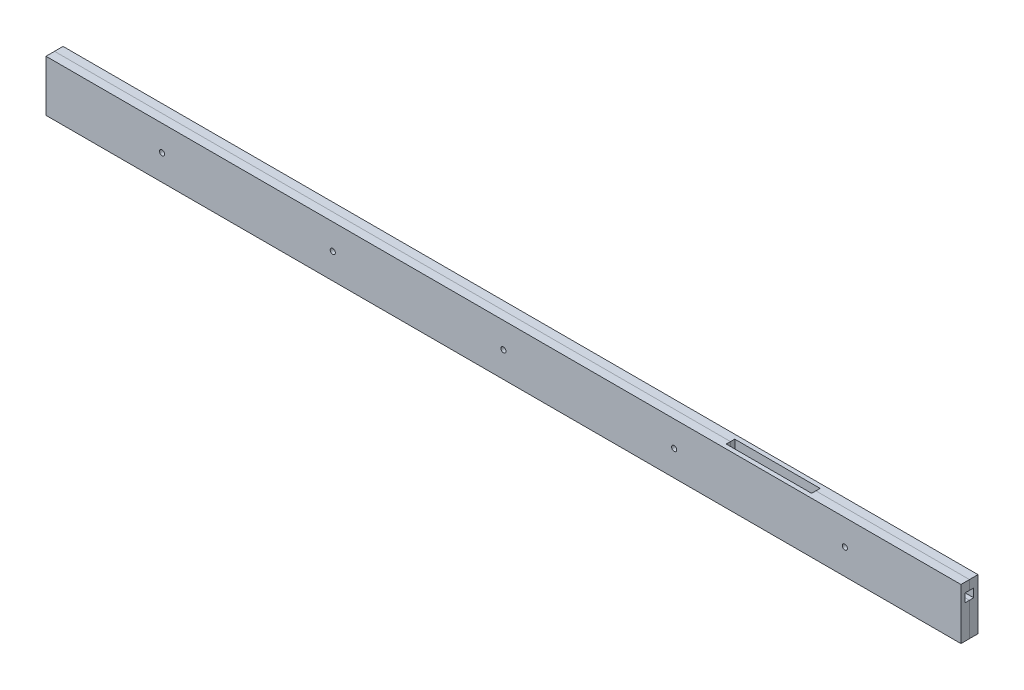
SolidWorks part; units mm, degrees
material "Настроенная пользователем пластмасса"
ref_plane "Спереди" through (0, 0, 0) normal (0, 0, 1) x (1, 0, 0)
ref_plane "Сверху" through (0, 0, 0) normal (0, 1, 0) x (1, 0, 0)
ref_plane "Справа" through (0, 0, 0) normal (1, 0, 0) x (0, 0, -1)
sketch "Эскиз1" plane through (0, 0, 0) normal (0, 0, 1) x (1, 0, 0)
  line L1 (-536, -30) -> (536, -30)
  line L2 (-536, -30) -> (-536, 30)
  line L3 (-536, 30) -> (536, 30)
  line L4 (536, -30) -> (536, 30)
  line L5 (0, 30) -> (0, -30) construction
  line L6 (-536, 0) -> (536, 0) construction
  point P0 (0, 0)
  dimension "D1" = 60
  dimension "D2" = 1072
extrude "Бобышка-Вытянуть1" add sketch "Эскиз1" along normal mid plane 10
sketch "Эскиз2" plane through (0, 0, 5) normal (0, 0, 1) x (1, 0, 0)
  line L1 (-291, 19) -> (256, 19)
  line L3 (-291, 9) -> (256, 9)
  line L4 (536, 19) -> (536, 9)
  line L5 (536, -30) -> (536, 30) construction
  line L6 (536, 30) -> (-536, 30) construction
  line L7 (-536, -30) -> (536, -30) construction
  line L8 (256, 30) -> (356, 30)
  line L9 (256, 30) -> (256, 19)
  line L10 (256, -30) -> (356, -30)
  line L11 (356, 30) -> (356, 19)
  line L12 (-536, 30) -> (-536, -30) construction
  line L13 (356, 19) -> (536, 19)
  line L14 (256, 9) -> (256, -30)
  line L15 (356, 9) -> (536, 9)
  line L16 (356, 9) -> (356, -30)
  arc A0 (-291, 9) -> (-291, 19) centre (-291, 14) cw
  dimension "D1" = 240
  dimension "D2" = 11
  dimension "D3" = 10
  dimension "D4" = 100
  dimension "D5" = 180
extrude "Вырез-Вытянуть1" cut sketch "Эскиз2" against normal blind 5
sketch "Эскиз3" plane through (0, 0, 5) normal (0, 0, 1) x (1, 0, 0)
  line L0 (356, -30) -> (536, -30) construction
  line L3 (400, 0) -> (536, 0) construction
  line L4 (536, -30) -> (536, 9) construction
  circle A0 centre (400, 0) radius 3
  dimension "D1" = 6
  dimension "D2" = 30
  dimension "D4" = 136
extrude "Вырез-Вытянуть2" cut sketch "Эскиз3" against normal through all
chamfer "Фаска1" distance 2 angle 45 1 edges at (403, 0, 5)
pattern_linear "Линейный массив1" count 5 spacing 200 along (-1, 0, 0) of "Вырез-Вытянуть2", "Фаска1"
mirror "Зеркальное отражение1" about plane through (0, 0, 5) normal (0, 0, -1) of bodies 107 104
